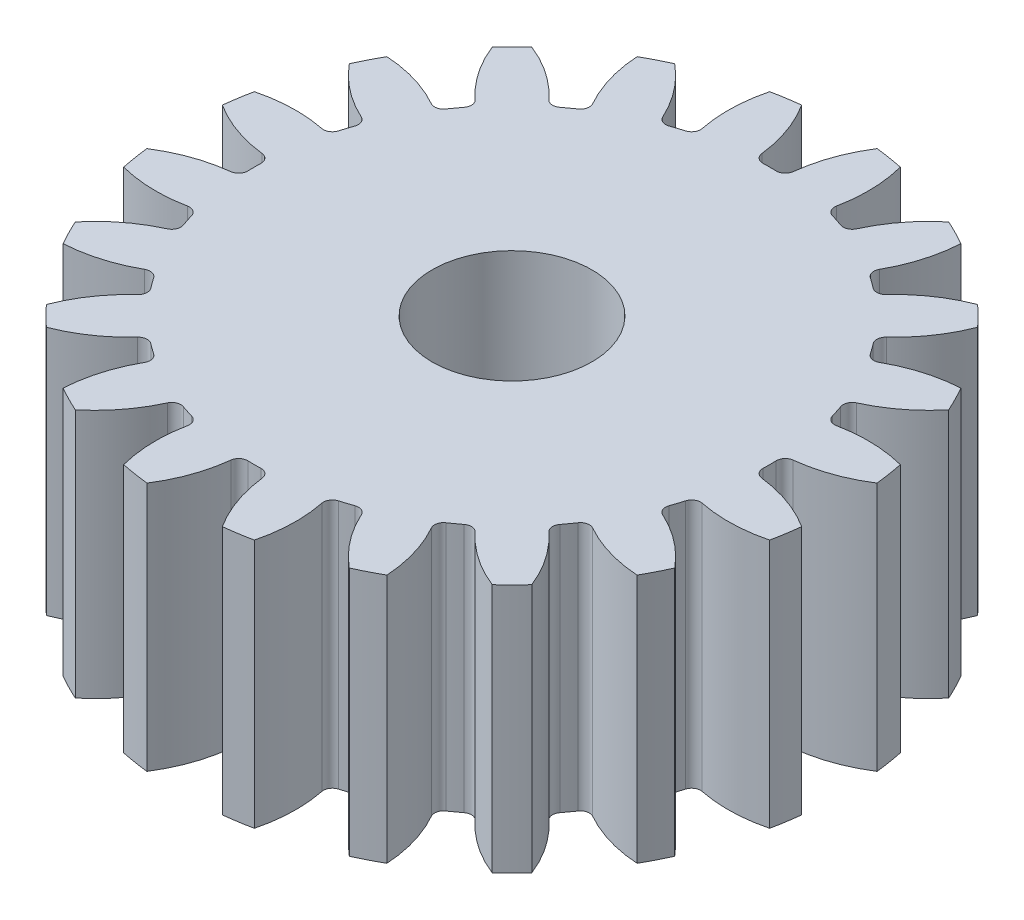
SolidWorks part; units mm, degrees
ref_plane "Ebene vorne" through (0, 0, 0) normal (0, 0, 1) x (1, 0, 0)
ref_plane "Ebene oben" through (0, 0, 0) normal (0, 1, 0) x (1, 0, 0)
ref_plane "Ebene rechts" through (0, 0, 0) normal (1, 0, 0) x (0, 0, -1)
sketch "Skizze1" plane through (0, 0, 0) normal (0, 1, 0) x (1, 0, 0)
  circle A0 centre (0, 0) radius 6
  circle A1 centre (0, 0) radius 1.6
  circle A2 centre (0, 0) radius 6.6
  circle A3 centre (0, 0) radius 5.16
  dimension "D1" = 12
  dimension "D2" = 3.2
  dimension "D3" = 0.6
  dimension "D4" = 1.44
extrude "Aufsatz-Linear austragen1" add sketch "Skizze1" along normal blind 5 contours A3 A1 | A0 A3 | A2 A0 region at (-5.8303, 0, 0) region at (-6.4133, 0, 0) region at (-5.0141, 0, 0)
sketch "Skizze2" plane through (0, 5, 0) normal (0, 1, 0) x (1, 0, 0)
  line L0 (0, 0) -> (0, 6.6) construction
  line L1 (-0.4708, 5.9815) -> (0.4708, 5.9815) construction
  line L2 (0, 0) -> (-0.2994, 5.1513) construction
  line L3 (0, 4.6881) -> (-0.7534, 6.7581) construction
  line L4 (0, 0) -> (1.0325, 6.5187) construction
  line L5 (0.4708, 5.9815) -> (1.4007, 5.8342) construction
  circle A0 centre (0, 0) radius 6 construction
  arc A1 (-0.8841, 6.7423) -> (-0.2994, 5.1513) centre (-3.2177, 4.9817) cw
  arc A2 (0.8841, 6.7423) -> (0.2994, 5.1513) centre (3.2177, 4.9817) ccw
  circle A3 centre (0, 0) radius 5.16 construction
  arc A4 (-0.2994, 5.1513) -> (0.2994, 5.1513) centre (0, 0) cw
  circle A5 centre (0, 0) radius 6.6 construction
  arc A6 (0.8841, 6.7423) -> (-0.8841, 6.7423) centre (0, 0) ccw
  dimension "D1" = 6.8
  dimension "D2" = 20
  dimension "D3" = 9
extrude "Schnitt-Linear austragen1" cut sketch "Skizze2" against normal through all
fillet "Verrundung1" radius 0.18 2 edges at (0.2994, 2.5, -5.1513) (-0.2994, 2.5, -5.1513)
pattern_circular "Kreismuster1" count 20 over 360 about axis through (0, 5, 0) along (0, -1, 0) of "Schnitt-Linear austragen1", "Verrundung1" reverse direction yes
equation "\"Tooth\"= 20"
equation "\"Module\"= 0.6mm"
equation "\"D1@Skizze1\"=\"Module\"*\"Tooth\""
equation "\"D3@Skizze1\"=\"Module\""
equation "\"D4@Skizze1\"=\"Module\"*if(\"Module\" => 1.25,2.25,2.4)"
equation "\"D3@Skizze2\"=180/\"Tooth\""
